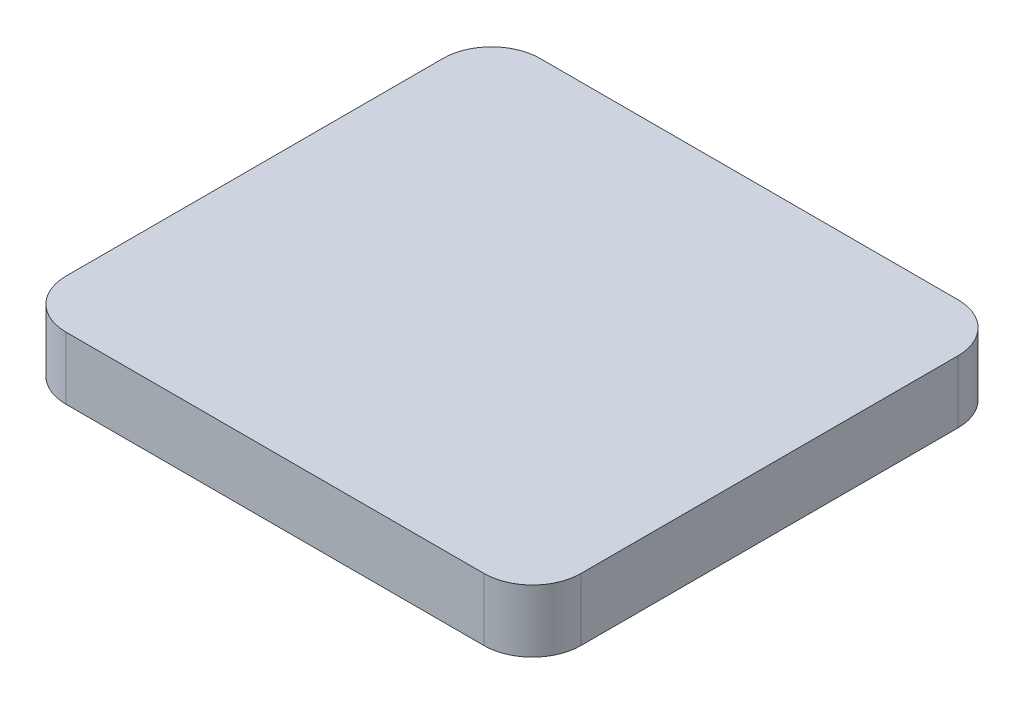
SolidWorks part; units mm, degrees
ref_plane "Front Plane" through (0, 0, 0) normal (0, 0, 1) x (1, 0, 0)
ref_plane "Top Plane" through (0, 0, 0) normal (0, 1, 0) x (1, 0, 0)
ref_plane "Right Plane" through (0, 0, 0) normal (1, 0, 0) x (0, 0, -1)
sketch "Sketch1" plane through (0, 0, 0) normal (0, 1, 0) x (1, 0, 0)
  line L0 (-21.9, 20) -> (-21.9, 22) construction
  line L1 (19.4, 20) -> (-19.4, 20)
  line L2 (21.9, 17.5) -> (21.9, -17.5)
  line L3 (19.4, -20) -> (-19.4, -20)
  line L4 (-21.9, 17.5) -> (-21.9, -17.5)
  line L5 (21.9, 20) -> (-21.9, -20) construction
  line L6 (21.9, -20) -> (-21.9, 20) construction
  line L7 (23.9, -22) -> (-23.9, -22)
  line L8 (23.9, -22) -> (23.9, 22)
  line L9 (23.9, 22) -> (-23.9, 22)
  line L10 (-23.9, -22) -> (-23.9, 22)
  line L11 (23.9, -22) -> (-23.9, 22) construction
  line L12 (23.9, 22) -> (-23.9, -22) construction
  line L13 (-21.9, 20) -> (-23.9, 20) construction
  arc A0 (-19.4, -20) -> (-21.9, -17.5) centre (-19.4, -17.5) cw
  arc A1 (21.9, -17.5) -> (19.4, -20) centre (19.4, -17.5) cw
  arc A2 (19.4, 20) -> (21.9, 17.5) centre (19.4, 17.5) cw
  arc A3 (-19.4, 20) -> (-21.9, 17.5) centre (-19.4, 17.5) ccw
  circle A4 centre (-19.4, 17.5) radius 4.5
  circle A5 centre (19.4, 17.5) radius 4.5
  circle A6 centre (19.4, -17.5) radius 4.5
  circle A7 centre (-19.4, -17.5) radius 4.5
  point P0 (0, 0)
  point P6 (0, 0)
  dimension "D4" = 2.5
  dimension "D1" = 43.8
  dimension "D2" = 40
  dimension "D3" = 2
extrude "Boss-Extrude1" add sketch "Sketch1" along normal blind 1.3 contours L1 A4 L4 A3 | A7 L4 A4 L10 | A7 L3 A0 L4 | A7 L7 A6 L3 | A6 L2 A1 L3 | A6 L8 A5 L2 | L2 A5 L1 A2 | A5 L9 A4 L1 region at (17.5292, 0, -20.1166) region at (0, 0, -21.0286) region at (-17.5292, 0, -20.1166) region at (22.9323, 0, 0) region at (23.2658, 0, 15.4336) region at (-22.9323, 0, 0) region at (0, 0, 21.0286) region at (-22.0166, 0, 15.6292)
sketch "Sketch2" plane through (0, 1.3, 0) normal (0, 1, 0) x (1, 0, 0)
  line L4 (-19.4, -22) -> (19.4, -22)
  line L5 (23.9, -17.5) -> (23.9, 17.5)
  line L6 (19.4, 22) -> (-19.4, 22)
  line L7 (-23.9, 17.5) -> (-23.9, -17.5)
  line L8 (-19.4, -22) -> (19.4, -22)
  line L9 (23.9, -17.5) -> (23.9, 17.5)
  line L10 (19.4, 22) -> (-19.4, 22)
  line L11 (-23.9, 17.5) -> (-23.9, -17.5)
  arc A4 (19.4, -22) -> (23.9, -17.5) centre (19.4, -17.5) ccw
  arc A5 (23.9, 17.5) -> (19.4, 22) centre (19.4, 17.5) ccw
  arc A6 (-19.4, 22) -> (-23.9, 17.5) centre (-19.4, 17.5) ccw
  arc A7 (-23.9, -17.5) -> (-19.4, -22) centre (-19.4, -17.5) ccw
  arc A8 (19.4, -22) -> (23.9, -17.5) centre (19.4, -17.5) ccw
  arc A9 (23.9, 17.5) -> (19.4, 22) centre (19.4, 17.5) ccw
  arc A10 (-19.4, 22) -> (-23.9, 17.5) centre (-19.4, 17.5) ccw
  arc A11 (-23.9, -17.5) -> (-19.4, -22) centre (-19.4, -17.5) ccw
  dimension "D1" = 0
extrude "Boss-Extrude2" add sketch "Sketch2" along normal blind 1.5
sketch "Sketch3" plane through (0, 1.3, 0) normal (0, -1, 0) x (1, 0, 0)
  line L0 (-23.9, 0) -> (23.9, 0) construction
  line L1 (-23.9, 17.5) -> (-23.9, -17.5) construction
  line L2 (23.9, 17.5) -> (23.9, -17.5) construction
  line L3 (-23.9, 11) -> (23.9, 11) construction
  line L4 (0, 11) -> (0, 22) construction
  line L5 (19.4, 22) -> (-19.4, 22) construction
  line L6 (0, 11) -> (0, 0) construction
  line L7 (-23.9, -11) -> (23.9, -11) construction
  line L8 (0, 0) -> (4.1348, 4.1348) construction
  line L9 (11, -23.9) -> (11, 23.9) construction
  line L10 (-11, -23.9) -> (-11, 23.9) construction
  line L11 (-21.9, -17.5) -> (-21.9, 17.5) construction
  line L12 (-21.9, -17.5) -> (-21.9, 17.5) construction
  line L13 (19.4, -20) -> (-19.4, -20) construction
  line L14 (21.9, -17.5) -> (21.9, 17.5) construction
  line L15 (19.4, 20) -> (-19.4, 20) construction
  line L16 (19.4, 20) -> (-19.4, 20) construction
  line L17 (0, 0) -> (0, -20) construction
  circle A0 centre (-21.9, 11) radius 0.4
  circle A1 centre (-21.9, 0) radius 0.4
  circle A2 centre (-21.9, -11) radius 0.4
  circle A3 centre (-11, -20) radius 0.4
  circle A4 centre (11, -20) radius 0.4
  circle A5 centre (21.9, -11) radius 0.4
  circle A6 centre (21.9, 0) radius 0.4
  circle A7 centre (21.9, 11) radius 0.4
  circle A8 centre (11, 20) radius 0.4
  circle A9 centre (0, 20) radius 0.4
  circle A10 centre (-11, 20) radius 0.4
  circle A11 centre (0, -20) radius 0.4
  dimension "D2" = 0.8
  dimension "D1" = 45
extrude "Boss-Extrude3" add sketch "Sketch3" along normal up to surface (1.3 mm away) up to face at (0, 0, 0)
sketch "Sketch4" plane through (0, 0, 0) normal (0, -1, 0) x (1, 0, 0)
  line L0 (-22.9, 17.5) -> (-22.9, -17.5)
  line L1 (-19.4, -21) -> (19.4, -21)
  line L2 (22.9, -17.5) -> (22.9, 17.5)
  line L3 (19.4, 21) -> (-19.4, 21)
  line L4 (19.4, 22) -> (-19.4, 22)
  line L5 (-23.9, 17.5) -> (-23.9, -17.5)
  line L6 (-19.4, -22) -> (19.4, -22)
  line L7 (23.9, -17.5) -> (23.9, 17.5)
  line L8 (19.4, 22) -> (-19.4, 22)
  line L9 (-23.9, 17.5) -> (-23.9, -17.5)
  line L10 (-19.4, -22) -> (19.4, -22)
  line L11 (23.9, -17.5) -> (23.9, 17.5)
  arc A0 (-19.4, 21) -> (-22.9, 17.5) centre (-19.4, 17.5) ccw
  arc A1 (-22.9, -17.5) -> (-19.4, -21) centre (-19.4, -17.5) ccw
  arc A2 (19.4, -21) -> (22.9, -17.5) centre (19.4, -17.5) ccw
  arc A3 (22.9, 17.5) -> (19.4, 21) centre (19.4, 17.5) ccw
  arc A4 (-19.4, 22) -> (-23.9, 17.5) centre (-19.4, 17.5) ccw
  arc A5 (-23.9, -17.5) -> (-19.4, -22) centre (-19.4, -17.5) ccw
  arc A6 (19.4, -22) -> (23.9, -17.5) centre (19.4, -17.5) ccw
  arc A7 (23.9, 17.5) -> (19.4, 22) centre (19.4, 17.5) ccw
  arc A8 (-19.4, 22) -> (-23.9, 17.5) centre (-19.4, 17.5) ccw
  arc A9 (-23.9, -17.5) -> (-19.4, -22) centre (-19.4, -17.5) ccw
  arc A10 (19.4, -22) -> (23.9, -17.5) centre (19.4, -17.5) ccw
  arc A11 (23.9, 17.5) -> (19.4, 22) centre (19.4, 17.5) ccw
  dimension "D1" = 0
  dimension "D2" = 1
extrude "Boss-Extrude4" add sketch "Sketch4" along normal blind 3
sketch "Sketch5" plane through (0, 1.3, 0) normal (0, -1, 0) x (1, 0, 0)
  line L16 (0.9798, -19) -> (10.0202, -19)
  line L17 (0.9798, -19) -> (10.0202, -19)
  line L31 (-11.9798, 19) -> (-19.4, 19)
  line L32 (-20.9, 17.5) -> (-20.9, 11.9798)
  line L33 (-20.9, 10.0202) -> (-20.9, 0.9798)
  line L34 (-20.9, -0.9798) -> (-20.9, -10.0202)
  line L35 (-20.9, -11.9798) -> (-20.9, -17.5)
  line L36 (-19.4, -19) -> (-11.9798, -19)
  line L37 (-10.0202, -19) -> (-0.9798, -19)
  line L38 (11.9798, -19) -> (19.4, -19)
  line L39 (20.9, -17.5) -> (20.9, -11.9798)
  line L40 (20.9, -10.0202) -> (20.9, -0.9798)
  line L41 (20.9, 0.9798) -> (20.9, 10.0202)
  line L42 (20.9, 11.9798) -> (20.9, 17.5)
  line L43 (19.4, 19) -> (11.9798, 19)
  line L44 (10.0202, 19) -> (0.9798, 19)
  line L45 (-0.9798, 19) -> (-10.0202, 19)
  line L46 (-11.9798, 19) -> (-19.4, 19)
  line L47 (-20.9, 17.5) -> (-20.9, 11.9798)
  line L48 (-20.9, 10.0202) -> (-20.9, 0.9798)
  line L49 (-20.9, -0.9798) -> (-20.9, -10.0202)
  line L50 (-20.9, -11.9798) -> (-20.9, -17.5)
  line L51 (-19.4, -19) -> (-11.9798, -19)
  line L52 (-10.0202, -19) -> (-0.9798, -19)
  line L53 (11.9798, -19) -> (19.4, -19)
  line L54 (20.9, -17.5) -> (20.9, -11.9798)
  line L55 (20.9, -10.0202) -> (20.9, -0.9798)
  line L56 (20.9, 0.9798) -> (20.9, 10.0202)
  line L57 (20.9, 11.9798) -> (20.9, 17.5)
  line L58 (19.4, 19) -> (11.9798, 19)
  line L59 (10.0202, 19) -> (0.9798, 19)
  line L60 (-0.9798, 19) -> (-10.0202, 19)
  arc A16 (0.9798, -19) -> (-0.9798, -19) centre (0, -20) ccw
  arc A17 (0.9798, -19) -> (-0.9798, -19) centre (0, -20) ccw
  arc A30 (-11.9798, 19) -> (-10.0202, 19) centre (-11, 20) ccw
  arc A31 (-19.4, 19) -> (-20.9, 17.5) centre (-19.4, 17.5) ccw
  arc A32 (-20.9, 10.0202) -> (-20.9, 11.9798) centre (-21.9, 11) ccw
  arc A33 (-20.9, -0.9798) -> (-20.9, 0.9798) centre (-21.9, 0) ccw
  arc A34 (-20.9, -11.9798) -> (-20.9, -10.0202) centre (-21.9, -11) ccw
  arc A35 (-20.9, -17.5) -> (-19.4, -19) centre (-19.4, -17.5) ccw
  arc A36 (-10.0202, -19) -> (-11.9798, -19) centre (-11, -20) ccw
  arc A37 (11.9798, -19) -> (10.0202, -19) centre (11, -20) ccw
  arc A38 (19.4, -19) -> (20.9, -17.5) centre (19.4, -17.5) ccw
  arc A39 (20.9, -10.0202) -> (20.9, -11.9798) centre (21.9, -11) ccw
  arc A40 (20.9, 0.9798) -> (20.9, -0.9798) centre (21.9, 0) ccw
  arc A41 (20.9, 11.9798) -> (20.9, 10.0202) centre (21.9, 11) ccw
  arc A42 (20.9, 17.5) -> (19.4, 19) centre (19.4, 17.5) ccw
  arc A43 (10.0202, 19) -> (11.9798, 19) centre (11, 20) ccw
  arc A44 (-0.9798, 19) -> (0.9798, 19) centre (0, 20) ccw
  arc A45 (-11.9798, 19) -> (-10.0202, 19) centre (-11, 20) ccw
  arc A46 (-19.4, 19) -> (-20.9, 17.5) centre (-19.4, 17.5) ccw
  arc A47 (-20.9, 10.0202) -> (-20.9, 11.9798) centre (-21.9, 11) ccw
  arc A48 (-20.9, -0.9798) -> (-20.9, 0.9798) centre (-21.9, 0) ccw
  arc A49 (-20.9, -11.9798) -> (-20.9, -10.0202) centre (-21.9, -11) ccw
  arc A50 (-20.9, -17.5) -> (-19.4, -19) centre (-19.4, -17.5) ccw
  arc A51 (-10.0202, -19) -> (-11.9798, -19) centre (-11, -20) ccw
  arc A52 (11.9798, -19) -> (10.0202, -19) centre (11, -20) ccw
  arc A53 (19.4, -19) -> (20.9, -17.5) centre (19.4, -17.5) ccw
  arc A54 (20.9, -10.0202) -> (20.9, -11.9798) centre (21.9, -11) ccw
  arc A55 (20.9, 0.9798) -> (20.9, -0.9798) centre (21.9, 0) ccw
  arc A56 (20.9, 11.9798) -> (20.9, 10.0202) centre (21.9, 11) ccw
  arc A57 (20.9, 17.5) -> (19.4, 19) centre (19.4, 17.5) ccw
  arc A58 (10.0202, 19) -> (11.9798, 19) centre (11, 20) ccw
  arc A59 (-0.9798, 19) -> (0.9798, 19) centre (0, 20) ccw
  dimension "D1" = 1
extrude "Cut-Extrude1" cut sketch "Sketch5" against normal blind 0.5
sketch "Sketch8" plane through (0, 0, 0) normal (0, -1, 0) x (1, 0, 0)
  line L0 (-11, 20) -> (-11, -20) construction
  line L1 (0, -20) -> (0, 20) construction
  line L2 (11, 20) -> (11, -20) construction
  line L3 (-21.9, 11) -> (21.9, 11) construction
  line L4 (21.9, 0) -> (-21.9, 0) construction
  line L5 (-21.9, -11) -> (21.9, -11) construction
  line L6 (19.4, 21) -> (-19.4, 21) construction
  line L7 (22.9, -17.5) -> (22.9, 17.5) construction
  line L8 (22.9, -17.5) -> (22.9, 17.5) construction
  line L9 (-19.4, -21) -> (19.4, -21) construction
  line L10 (-22.9, 17.5) -> (-22.9, -17.5) construction
  line L11 (-22.9, 17.5) -> (-22.9, -17.5) construction
  circle A0 centre (-11, 21) radius 0.4
  arc A1 (-11.4, 20) -> (-10.6, 20) centre (-11, 20) ccw construction
  circle A2 centre (0, 21) radius 0.4
  circle A3 centre (11, 21) radius 0.4
  circle A4 centre (22.9, 11) radius 0.4
  circle A5 centre (-22.9, 11) radius 0.4
  circle A6 centre (-22.9, 0) radius 0.4
  circle A7 centre (22.9, 0) radius 0.4
  circle A8 centre (22.9, -11) radius 0.4
  circle A9 centre (11, -21) radius 0.4
  circle A10 centre (0, -21) radius 0.4
  circle A11 centre (-11, -21) radius 0.4
  circle A12 centre (-22.9, -11) radius 0.4
  point P53 (0, 21)
  point P54 (11, 21)
  point P55 (22.9, 11)
  point P58 (22.9, 0)
  point P59 (22.9, -11)
  point P62 (11, -21)
  point P65 (0, -21)
  point P66 (-11, -21)
  point P67 (-11, -21)
  point P68 (-22.9, -11)
  point P71 (-22.9, 0)
  point P72 (-22.9, 11)
  point P73 (-22.9, 11)
extrude "Boss-Extrude5" add sketch "Sketch8" along normal up to surface (3 mm away) up to face at (0, -3, 0)
